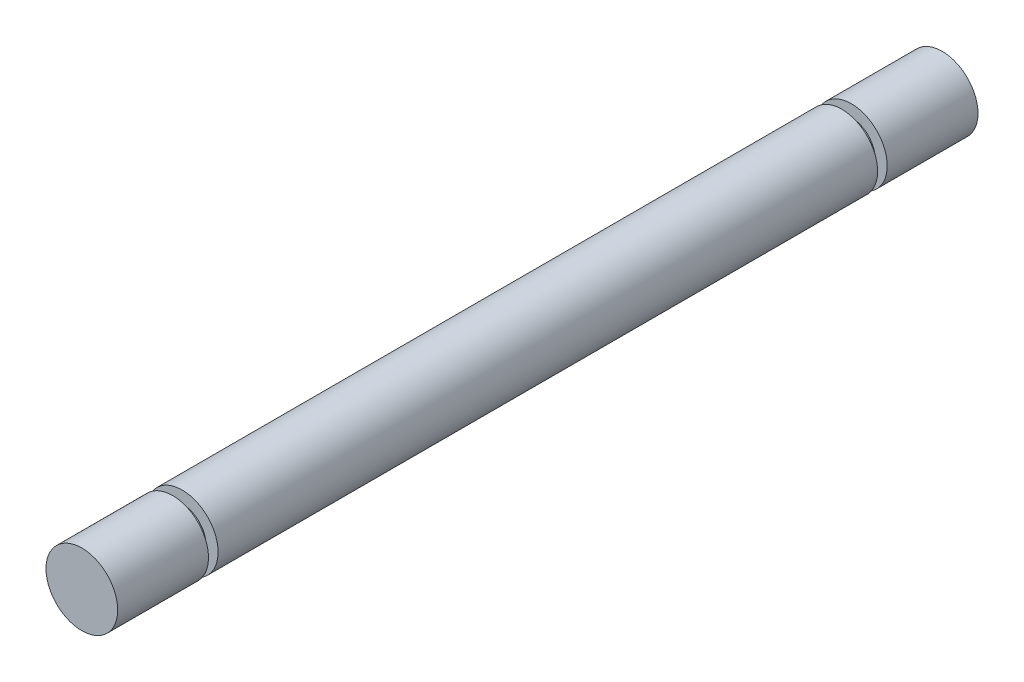
SolidWorks part; units mm, degrees
ref_plane "Front Plane" through (0, 0, 0) normal (0, 0, 1) x (1, 0, 0)
ref_plane "Top Plane" through (0, 0, 0) normal (0, 1, 0) x (1, 0, 0)
ref_plane "Right Plane" through (0, 0, 0) normal (1, 0, 0) x (0, 0, -1)
sketch "Sketch1" plane through (0, 0, 0) normal (0, 0, 1) x (1, 0, 0)
  circle A0 centre (0, 0) radius 4.7625
  dimension "D1" = 9.525
extrude "Boss-Extrude1" add sketch "Sketch1" along normal blind 87.63
sketch "Sketch2" plane through (0, 0, 0) normal (0, 0, -1) x (-1, 0, 0)
  circle A0 centre (0, 0) radius 3.175
  dimension "D1" = 6.35
extrude "Boss-Extrude2" add sketch "Sketch2" along normal blind 1.27
sketch "Sketch3" plane through (0, 0, -1.27) normal (0, 0, -1) x (-1, 0, 0)
  circle A0 centre (0, 0) radius 4.7625
  dimension "D1" = 9.525
extrude "Boss-Extrude3" add sketch "Sketch3" along normal blind 12.065
sketch "Sketch4" plane through (0, 0, 87.63) normal (0, 0, 1) x (1, 0, 0)
  circle A0 centre (0, 0) radius 3.175
  dimension "D1" = 6.35
extrude "Boss-Extrude4" add sketch "Sketch4" along normal blind 1.27
sketch "Sketch5" plane through (0, 0, 88.9) normal (0, 0, 1) x (1, 0, 0)
  circle A0 centre (0, 0) radius 4.7625
  dimension "D1" = 9.525
extrude "Boss-Extrude5" add sketch "Sketch5" along normal blind 12.065
